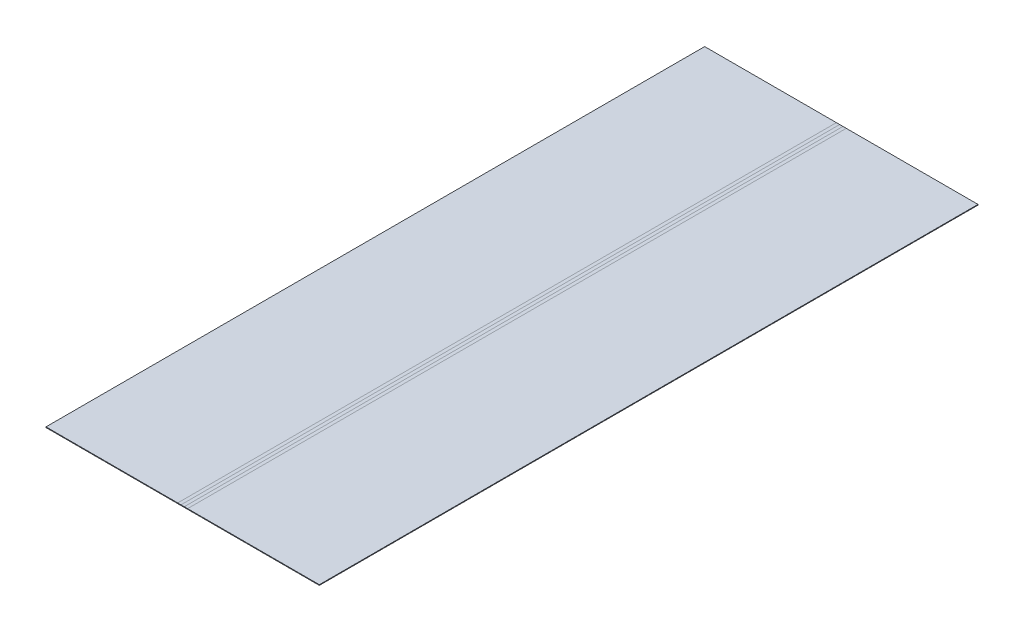
SolidWorks part; units mm, degrees
other "Caméra1"
ref_plane "Plan de face" through (0, 0, 0) normal (0, 0, 1) x (1, 0, 0)
ref_plane "Plan de dessus" through (0, 0, 0) normal (0, 1, 0) x (1, 0, 0)
ref_plane "Plan de droite" through (0, 0, 0) normal (1, 0, 0) x (0, 0, -1)
sketch "Esquisse1" plane through (0, 0, 0) normal (0, 1, 0) x (1, 0, 0)
  line L0 (0, 0) -> (0, 114.0728) construction
  line L1 (-75, -5000) -> (-2075, 5000) construction
  line L2 (-25, -5000) -> (25, -5000)
  line L3 (-25, -5000) -> (-25, 5000)
  line L4 (-25, 5000) -> (25, 5000)
  line L5 (25, -5000) -> (25, 5000)
  line L6 (-25, -5000) -> (25, 5000) construction
  line L7 (-25, 5000) -> (25, -5000) construction
  line L8 (25, 5000) -> (75, 5000)
  line L9 (25, 5000) -> (25, -5000)
  line L10 (25, -5000) -> (75, -5000)
  line L11 (75, 5000) -> (75, -5000)
  line L12 (25, 5000) -> (75, -5000) construction
  line L13 (25, -5000) -> (75, 5000) construction
  line L14 (75, 5000) -> (2075, 5000)
  line L15 (75, 5000) -> (75, -5000)
  line L16 (75, -5000) -> (2075, -5000)
  line L17 (2075, 5000) -> (2075, -5000)
  line L18 (75, 5000) -> (2075, -5000) construction
  line L19 (75, -5000) -> (2075, 5000) construction
  line L20 (-75, 5000) -> (-2075, -5000) construction
  line L21 (-25, -5000) -> (-75, 5000) construction
  line L22 (-25, 5000) -> (-75, -5000) construction
  line L23 (-2075, 5000) -> (-2075, -5000)
  line L24 (-75, -5000) -> (-2075, -5000)
  line L25 (-75, 5000) -> (-75, -5000)
  line L26 (-75, 5000) -> (-2075, 5000)
  line L27 (-75, 5000) -> (-75, -5000)
  line L28 (-25, -5000) -> (-75, -5000)
  line L29 (-25, 5000) -> (-25, -5000)
  line L30 (-25, 5000) -> (-75, 5000)
  line L31 (-25, -5000) -> (-25, 5000)
  point P7 (0, 0)
  point P11 (50, 0)
  point P13 (1075, 0)
  point P18 (-1075, 0)
  point P19 (-50, 0)
  dimension "D1" = 50
  dimension "D2" = 10000
  dimension "D3" = 50
  dimension "D4" = 2000
extrude "Boss.-Extru.2" add sketch "Esquisse1" along normal blind 10 contours L2 L5 L4 L3 region at (0, 0, 0)
extrude "Boss.-Extru.3" add sketch "Esquisse1<4>" along normal blind 10 separate body contours L3 L30 L25 L28 | L11 L8 L5 L10 region at (-50, 0, 0) region at (50, 0, 0)
sketch "Esquisse1<4>" plane through (0, 0, 0) normal (0, 1, 0) x (1, 0, 0) same geometry as "Esquisse1"
extrude "Boss.-Extru.4" add sketch "Esquisse1<5>" along normal blind 10 separate body contours L25 L26 L23 L24 | L17 L14 L11 L16 region at (-1075, 0, 0) region at (1075, 0, 0)
sketch "Esquisse1<5>" plane through (0, 0, 0) normal (0, 1, 0) x (1, 0, 0) same geometry as "Esquisse1"
